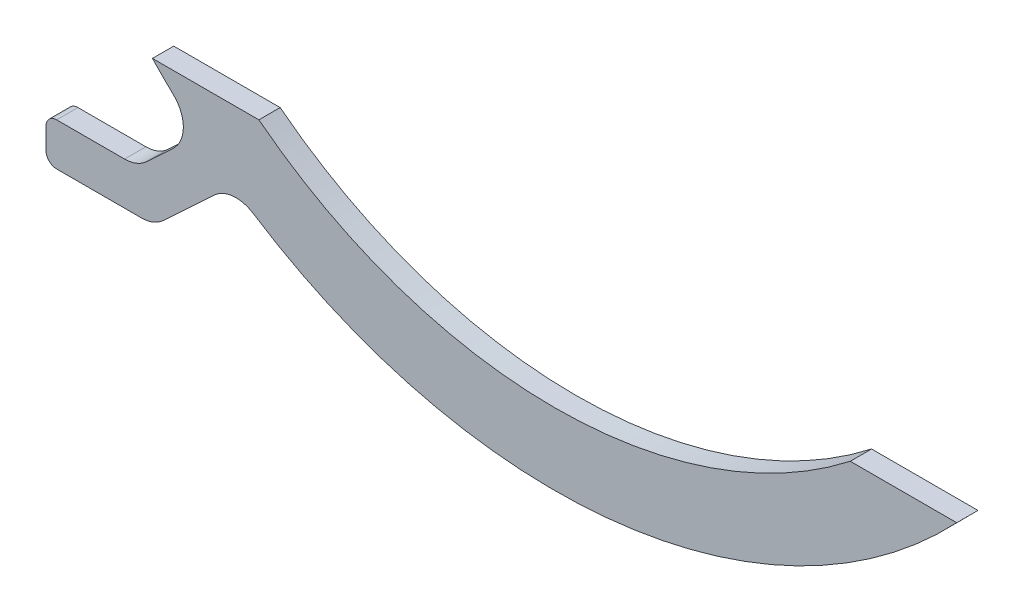
SolidWorks part; units mm, degrees
ref_plane "Front" through (0, 0, 0) normal (0, 0, 1) x (1, 0, 0)
ref_plane "Top" through (0, 0, 0) normal (0, 1, 0) x (1, 0, 0)
ref_plane "Right" through (0, 0, 0) normal (1, 0, 0) x (0, 0, -1)
sketch "Sketch1" plane through (0, 0, 0) normal (0, 0, 1) x (1, 0, 0)
  line L0 (230.378, -3.175) -> (198.628, -3.175)
  line L1 (211.328, -3.175) -> (239.903, -3.175) construction
  line L2 (-9.525, -3.175) -> (22.225, -3.175)
  line L3 (9.525, -3.175) -> (-31.75, -3.175) construction
  line L6 (9.525, -3.175) -> (22.225, -3.175) construction
  arc A0 (230.378, -3.175) -> (-9.525, -3.175) centre (110.4265, 110.2695) cw
  arc A1 (198.628, -3.175) -> (22.225, -3.175) centre (110.4265, 110.2695) cw
  dimension "D5" = 165.1
  dimension "D1" = 12.7
  dimension "D2" = 31.75
  dimension "D3" = 12.7
extrude "Extrude1" add sketch "Sketch1" along normal mid plane 6.35
sketch "Sketch2" plane through (0, 0, -3.175) normal (0, 0, -1) x (-1, 0, 0)
  line L0 (41.275, -46.0375) -> (9.0795, -46.0375)
  line L1 (9.0795, -46.0375) -> (-14.4655, -24.0789)
  line L2 (41.275, -46.0375) -> (41.275, -33.3375)
  line L3 (41.275, -33.3375) -> (14.0826, -33.3375)
  line L4 (14.0826, -33.3375) -> (-4.2949, -16.1983)
  line L5 (41.275, 6.35) -> (41.275, 212.725) construction
  line L7 (26.0985, 22.225) -> (26.0985, 38.1) construction
  line L10 (-198.628, -3.175) -> (-230.378, -3.175)
  line L11 (9.525, -3.175) -> (-22.225, -3.175)
  arc A1 (-230.378, -3.175) -> (9.525, -3.175) centre (-110.4265, 110.2695) ccw construction
  arc A4 (-198.628, -3.175) -> (-22.225, -3.175) centre (-110.4265, 110.2695) ccw
  arc A5 (-230.378, -3.175) -> (9.525, -3.175) centre (-110.4265, 110.2695) ccw
  arc A7 (-14.4655, -24.0789) -> (-4.2949, -16.1983) centre (-110.4265, 110.2695) ccw
  point P15 (26.0985, 30.1625)
  dimension "D1" = 12.7
  dimension "D2" = 76.2
  dimension "D3" = 12.7
  dimension "D4" = 0
extrude "Extrude2" add sketch "Sketch2" against normal up to surface (6.35 mm away) up to face at (110.4265, -23.6523, 3.175)
fillet "Fillet1" radius 9.525 4 edges at (4.2949, -16.1983, 0) (-14.0826, -33.3375, 0) (14.4655, -24.0789, 0) (-9.0795, -46.0375, 0)
fillet "Fillet2" radius 3.175 2 edges at (-41.275, -33.3375, 0) (-41.275, -46.0375, 0)
